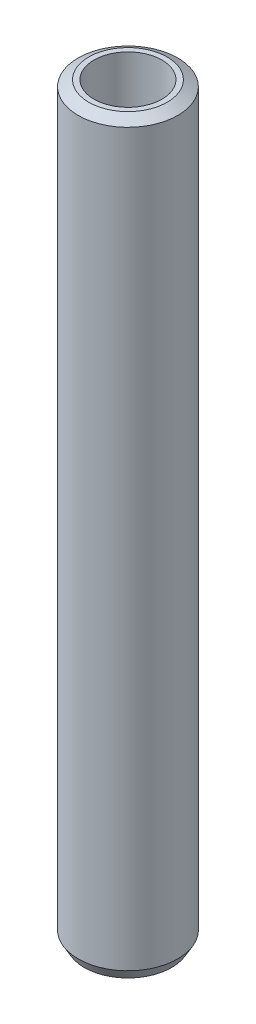
SolidWorks part; units mm, degrees
ref_plane "Front Plane" through (0, 0, 0) normal (0, 0, 1) x (1, 0, 0)
ref_plane "Top Plane" through (0, 0, 0) normal (0, 1, 0) x (1, 0, 0)
ref_plane "Right Plane" through (0, 0, 0) normal (1, 0, 0) x (0, 0, -1)
sketch "Sketch1" plane through (0, 0, 0) normal (0, 1, 0) x (1, 0, 0)
  circle A0 centre (0, 0) radius 40
  dimension "SHAFT_OD" = 80
extrude "Boss-Extrude1" add sketch "Sketch1" along normal blind 600
sketch "Sketch2" plane through (0, 0, 0) normal (0, 1, 0) x (1, 0, 0)
  circle A0 centre (0, 0) radius 27.2857
  dimension "BORE_D" = 54.5715
extrude "Cut-Extrude1" cut sketch "Sketch2" along normal through all
chamfer "Chamfer1" distance 4.9068 angle 60 2 edges at (0, 600, 40) (0, 0, 40) first distance on face at (0, 600, 40) first distance on face at (0, 0, 27.2857)
